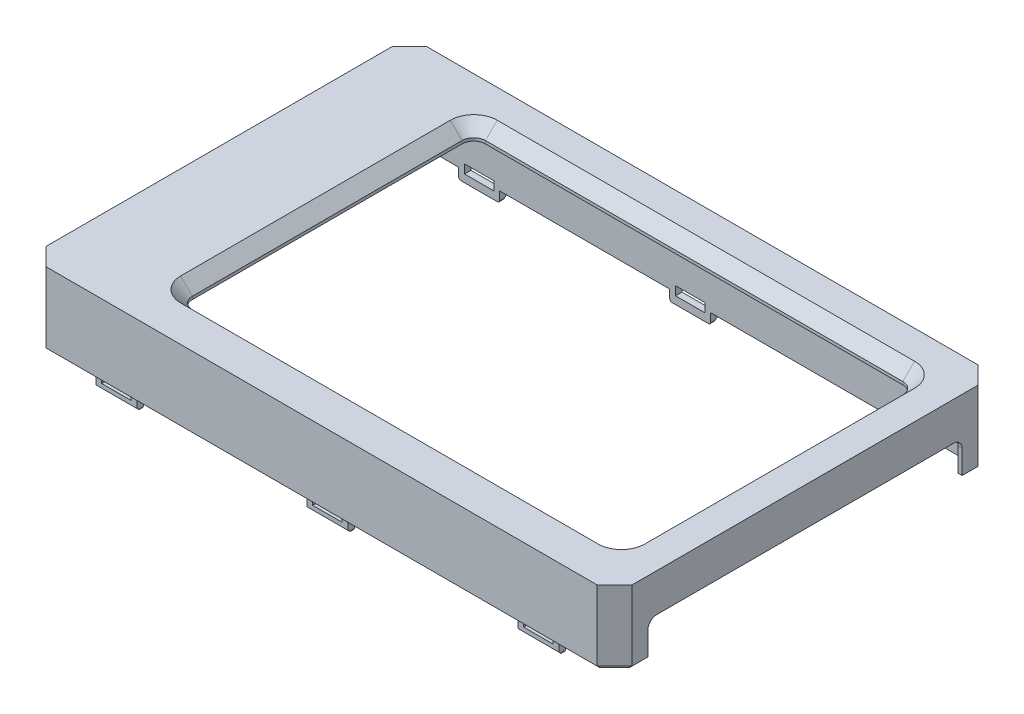
SolidWorks part; units mm, degrees
ref_plane "前视基准面" through (0, 0, 0) normal (0, 0, 1) x (1, 0, 0)
ref_plane "上视基准面" through (0, 0, 0) normal (0, 1, 0) x (1, 0, 0)
ref_plane "右视基准面" through (0, 0, 0) normal (1, 0, 0) x (0, 0, -1)
sketch "草图1" plane through (0, 0, 0) normal (0, 1, 0) x (1, 0, 0)
  line L1 (-50, 32.5) -> (50, 32.5)
  line L2 (-50, 32.5) -> (-50, -32.5)
  line L3 (-50, -32.5) -> (50, -32.5)
  line L4 (50, 32.5) -> (50, -32.5)
  line L5 (-50, 32.5) -> (50, -32.5) construction
  line L6 (-50, -32.5) -> (50, 32.5) construction
  point P0 (0, 0)
  dimension "D1" = 100
  dimension "D2" = 65
extrude "凸台-拉伸1" add sketch "草图1" along normal blind 2
sketch "草图4" plane through (0, 0, 0) normal (0, -1, 0) x (1, 0, 0)
  line L4 (-50, -32.5) -> (50, -32.5)
  line L5 (50, -32.5) -> (50, 32.5)
  line L6 (50, 32.5) -> (-50, 32.5)
  line L7 (-50, 32.5) -> (-50, -32.5)
  line L8 (-47.9, -30.4) -> (47.9, -30.4)
  line L9 (47.9, -30.4) -> (47.9, 30.4)
  line L10 (47.9, 30.4) -> (-47.9, 30.4)
  line L11 (-47.9, 30.4) -> (-47.9, -30.4)
  line L12 (-47.9, -30.4) -> (47.9, -30.4)
  line L13 (47.9, -30.4) -> (47.9, 30.4)
  line L14 (47.9, 30.4) -> (-47.9, 30.4)
  line L15 (-47.9, 30.4) -> (-47.9, -30.4)
  line L16 (-50, -32.5) -> (50, -32.5)
  line L17 (50, -32.5) -> (50, 32.5)
  line L18 (50, 32.5) -> (-50, 32.5)
  line L19 (-50, 32.5) -> (-50, -32.5)
  dimension "D1" = 2.1
  dimension "D2" = 0
extrude "凸台-拉伸2" add sketch "草图4" along normal blind 10
sketch "草图21" plane through (-50, 0, 0) normal (-1, 0, 0) x (0, 0, 1)
  line L0 (-32.5, 2) -> (32.5, 2) construction
  line L1 (-10, -2) -> (10, -2)
  line L2 (-10, -2) -> (-10, -4)
  line L3 (-10, -4) -> (10, -4)
  line L4 (10, -2) -> (10, -4)
  line L5 (-10, -2) -> (10, -4) construction
  line L6 (-10, -4) -> (10, -2) construction
  point P0 (0, -3)
  point P8 (0, 2)
  dimension "D1" = 4
  dimension "D2" = 2
  dimension "D3" = 20
chamfer "倒角4" distance 2 angle 45 4 edges at (47.9, -5, -30.4) (-47.9, -5, -30.4) (-47.9, -5, 30.4) (47.9, -5, 30.4)
chamfer "倒角5" distance 3 angle 45 4 edges at (-50, -4, -32.5) (-50, -4, 32.5) (50, -4, -32.5) (50, -4, 32.5)
sketch "草图24" plane through (47.9, 0, 0) normal (-1, 0, 0) x (0, 0, 1)
  line L0 (-28.4, -10) -> (28.4, -10) construction
  line L1 (-28.3, -10) -> (28.3, -10)
  line L2 (-28.3, -10) -> (-28.3, -4)
  line L3 (-28.3, -4) -> (28.3, -4)
  line L4 (28.3, -10) -> (28.3, -4)
  line L6 (-32.5, 2) -> (-32.5, -10) construction
  line L7 (32.5, -10) -> (32.5, 2) construction
  point P12 (0, 0)
  point P13 (-28.3, -1)
  point P14 (0, 0)
  point P15 (0, 0)
  point P16 (0, 0)
  point P17 (0, 0)
  point P18 (0, 0)
  point P19 (-28.3, -1)
  point P20 (0, 0)
  point P21 (0, 0)
  point P22 (0, 0)
  point P23 (28.3, -1)
  dimension "D1" = 4.2
  dimension "D2" = 4.2
  dimension "D3" = 6
extrude "切除-拉伸8" cut sketch "草图24" against normal blind 1.4
fillet "圆角9" radius 2 2 edges at (48.6, -4, 28.3) (48.6, -4, -28.3)
sketch "草图25" plane through (49.3, 0, 0) normal (-1, 0, 0) x (0, 0, 1)
  line L0 (-32.5, 2) -> (-32.5, -10) construction
  line L1 (32.5, -10) -> (32.5, 2) construction
  line L2 (29.5, -10) -> (-29.5, -10) construction
  line L4 (-28.3, -10) -> (28.3, -10) construction
  line L12 (26.8, -10) -> (26.8, -6)
  line L13 (25.3, -4.5) -> (-25.3, -4.5)
  line L14 (-26.8, -6) -> (-26.8, -10)
  line L15 (-26.8, -10) -> (26.8, -10)
  arc A6 (26.8, -6) -> (25.3, -4.5) centre (25.3, -6) ccw
  arc A7 (-25.3, -4.5) -> (-26.8, -6) centre (-25.3, -6) ccw
  point P0 (26.8, -10)
  dimension "D1" = 7.2
  dimension "D2" = 7.2
  dimension "D3" = 5.5
  dimension "D4" = 4
extrude "切除-拉伸9" cut sketch "草图25" against normal blind 11.4
sketch "草图26" plane through (0, -10, 0) normal (0, -1, 0) x (1, 0, 0)
  line L0 (45.9, 30.4) -> (47.9, 28.4)
  line L1 (-45.9, -30.4) -> (45.9, -30.4)
  line L2 (-47.9, -28.4) -> (-47.9, 28.4)
  line L3 (-45.9, 30.4) -> (45.9, 30.4)
  line L5 (-47.9, 28.4) -> (-45.9, 30.4)
  line L6 (-47.9, -28.4) -> (-45.9, -30.4)
  line L7 (45.9, -30.4) -> (47.9, -28.4)
  line L8 (-49, -28.8556) -> (-49, 28.8556)
  line L9 (-49, 28.8556) -> (-46.3556, 31.5)
  line L10 (-46.3556, 31.5) -> (46.3556, 31.5)
  line L11 (46.3556, 31.5) -> (49, 28.8556)
  line L13 (46.3556, -31.5) -> (49, -28.8556)
  line L14 (-46.3556, -31.5) -> (46.3556, -31.5)
  line L15 (-49, -28.8556) -> (-46.3556, -31.5)
  line L16 (45.9, 30.4) -> (-45.9, 30.4) construction
  line L17 (49, -28.8556) -> (49, 28.8556) construction
  line L18 (47.9, -28.4) -> (47.9, 28.4) construction
  line L19 (49, 28.8556) -> (49, 28.3)
  line L21 (49, 28.3) -> (47.9, 28.3)
  line L23 (47.9, 28.3) -> (47.9, 28.4)
  line L24 (49, -28.8556) -> (49, -28.3)
  line L26 (49, -28.3) -> (47.9, -28.3)
  line L28 (47.9, -28.3) -> (47.9, -28.4)
  line L29 (49.3, -28.3) -> (47.9, -28.3) construction
  line L30 (49.3, 28.3) -> (47.9, 28.3) construction
  point P0 (-47.9, -30.4)
  point P1 (47.9, 30.4)
  point P2 (-47.9, 30.4)
  point P3 (47.9, -30.4)
  dimension "D2" = 56.8
  dimension "D7" = 91.8
  dimension "D1" = 1.1
extrude "凸台-拉伸9" add sketch "草图26" along normal blind 1
sketch "草图30" plane through (0, 0, 0) normal (0, -1, 0) x (1, 0, 0)
  line L0 (50, 25.3) -> (50, -25.3) construction
  line L1 (45.3834, 10.75) -> (47.8, 10.75)
  line L2 (45.3834, 10.75) -> (45.3834, 9.25)
  line L3 (45.3834, 9.25) -> (47.8, 9.25)
  line L4 (47.8, 10.75) -> (47.8, 9.25)
  line L5 (45.3834, -7.25) -> (47.8, -7.25)
  line L6 (45.3834, -7.25) -> (45.3834, -8.75)
  line L7 (45.3834, -8.75) -> (47.8, -8.75)
  line L8 (47.8, -7.25) -> (47.8, -8.75)
  dimension "D1" = 2.2
  dimension "D2" = 2.4166
  dimension "D3" = 1.5
  dimension "D4" = 1.5
extrude "凸台-拉伸10" add sketch "草图30" along normal blind 6.3
chamfer "倒角8" distance 1 angle 45 2 edges at (47.8, -6.3, 10) (47.8, -6.3, -8)
sketch "草图33" plane through (-47.9, 0, 0) normal (1, 0, 0) x (0, 0, -1)
  line L1 (-7.5, -13) -> (-6, -13)
  line L2 (-7.5, -13) -> (-7.5, 0)
  line L3 (-7.5, 0) -> (-6, 0)
  line L4 (-6, -13) -> (-6, 0)
  line L6 (6, -13) -> (7.5, -13)
  line L7 (6, -13) -> (6, 0)
  line L8 (6, 0) -> (7.5, 0)
  line L9 (7.5, -13) -> (7.5, 0)
  line L10 (-32.5, -10) -> (-32.5, 2) construction
  line L11 (32.5, 2) -> (32.5, -10) construction
  line L12 (26.5, 0) -> (28, 0) construction
  line L13 (-28.4, 0) -> (28.4, 0) construction
  dimension "D1" = 25
  dimension "D2" = 25
  dimension "D3" = 13
  dimension "D4" = 1.5
extrude "凸台-拉伸11" add sketch "草图33" along normal blind 2
extrude "切除-拉伸15" cut sketch "草图21" against normal blind 5
fillet "圆角11" radius 1 4 edges at (-48.95, -2, -10) (-48.95, -4, -10) (-48.95, -2, 10) (-48.95, -4, 10)
chamfer "倒角9" distance 1 angle 45 2 edges at (-47.9, -13, 6.75) (-47.9, -13, -6.75)
sketch "草图34" plane through (0, 0, -30.4) normal (0, 0, 1) x (1, 0, 0)
  line L0 (47, -10) -> (-47, -10) construction
  line L1 (32.5, -10) -> (39.5, -10)
  line L2 (32.5, -10) -> (32.5, -12.8)
  line L3 (32.5, -12.8) -> (39.5, -12.8)
  line L4 (39.5, -10) -> (39.5, -12.8)
  line L6 (-3.5, -10) -> (3.5, -10)
  line L7 (-3.5, -10) -> (-3.5, -12.8)
  line L8 (-3.5, -12.8) -> (3.5, -12.8)
  line L9 (3.5, -10) -> (3.5, -12.8)
  line L10 (-39.5, -10) -> (-32.5, -10)
  line L11 (-39.5, -10) -> (-39.5, -12.8)
  line L12 (-39.5, -12.8) -> (-32.5, -12.8)
  line L13 (-32.5, -10) -> (-32.5, -12.8)
  dimension "D1" = 10.5
  dimension "D2" = 7
  dimension "D3" = 29
  dimension "D4" = 2.8
  dimension "D5" = 29
extrude "凸台-拉伸12" add sketch "草图34" against normal blind 1.1
sketch "草图35" plane through (0, 0, 30.4) normal (0, 0, -1) x (-1, 0, 0)
  line L4 (39.5, -10) -> (32.5, -10)
  line L5 (32.5, -10) -> (32.5, -12.8)
  line L6 (32.5, -12.8) -> (39.5, -12.8)
  line L7 (39.5, -12.8) -> (39.5, -10)
  line L8 (39.5, -10) -> (32.5, -10)
  line L9 (32.5, -10) -> (32.5, -12.8)
  line L10 (32.5, -12.8) -> (39.5, -12.8)
  line L11 (39.5, -12.8) -> (39.5, -10)
  line L12 (3.5, -10) -> (-3.5, -10)
  line L13 (-3.5, -10) -> (-3.5, -12.8)
  line L14 (-3.5, -12.8) -> (3.5, -12.8)
  line L15 (3.5, -12.8) -> (3.5, -10)
  line L16 (3.5, -10) -> (-3.5, -10)
  line L17 (-3.5, -10) -> (-3.5, -12.8)
  line L18 (-3.5, -12.8) -> (3.5, -12.8)
  line L19 (3.5, -12.8) -> (3.5, -10)
  line L20 (-32.5, -10) -> (-39.5, -10)
  line L21 (-39.5, -10) -> (-39.5, -12.8)
  line L22 (-39.5, -12.8) -> (-32.5, -12.8)
  line L23 (-32.5, -12.8) -> (-32.5, -10)
  line L24 (-32.5, -10) -> (-39.5, -10)
  line L25 (-39.5, -10) -> (-39.5, -12.8)
  line L26 (-39.5, -12.8) -> (-32.5, -12.8)
  line L27 (-32.5, -12.8) -> (-32.5, -10)
  dimension "D1" = 0
  dimension "D2" = 0
  dimension "D3" = 0
extrude "凸台-拉伸13" add sketch "草图35" against normal blind 1.1
sketch "草图36" plane through (0, 0, 31.5) normal (0, 0, 1) x (1, 0, 0)
  line L0 (46.3556, -10) -> (-46.3556, -10) construction
  line L1 (-33.5, -10) -> (-38.5, -10)
  line L2 (-33.5, -10) -> (-33.5, -11.5)
  line L3 (-33.5, -11.5) -> (-38.5, -11.5)
  line L4 (-38.5, -10) -> (-38.5, -11.5)
  line L5 (-50, -10) -> (-50, 2) construction
  line L6 (2.5, -10) -> (-2.5, -10)
  line L7 (2.5, -10) -> (2.5, -11.5)
  line L8 (2.5, -11.5) -> (-2.5, -11.5)
  line L9 (-2.5, -10) -> (-2.5, -11.5)
  line L10 (38.5, -10) -> (33.5, -10)
  line L11 (38.5, -10) -> (38.5, -11.5)
  line L12 (38.5, -11.5) -> (33.5, -11.5)
  line L13 (33.5, -10) -> (33.5, -11.5)
  point P16 (38.5, -8.5)
  dimension "D1" = 11.5
  dimension "D2" = 5
  dimension "D3" = 1.5
  dimension "D4" = 31
  dimension "D5" = 31
extrude "切除-拉伸16" cut sketch "草图36" against normal up to next
sketch "草图37" plane through (0, 0, -31.5) normal (0, 0, -1) x (-1, 0, 0)
  line L4 (-33.5, -10) -> (-38.5, -10)
  line L5 (-33.5, -11.5) -> (-33.5, -10)
  line L6 (-38.5, -11.5) -> (-33.5, -11.5)
  line L7 (-38.5, -10) -> (-38.5, -11.5)
  line L8 (-33.5, -10) -> (-38.5, -10)
  line L9 (-33.5, -11.5) -> (-33.5, -10)
  line L10 (-38.5, -11.5) -> (-33.5, -11.5)
  line L11 (-38.5, -10) -> (-38.5, -11.5)
  line L12 (2.5, -10) -> (-2.5, -10)
  line L13 (2.5, -11.5) -> (2.5, -10)
  line L14 (-2.5, -11.5) -> (2.5, -11.5)
  line L15 (-2.5, -10) -> (-2.5, -11.5)
  line L16 (2.5, -10) -> (-2.5, -10)
  line L17 (2.5, -11.5) -> (2.5, -10)
  line L18 (-2.5, -11.5) -> (2.5, -11.5)
  line L19 (-2.5, -10) -> (-2.5, -11.5)
  line L20 (38.5, -10) -> (33.5, -10)
  line L21 (38.5, -11.5) -> (38.5, -10)
  line L22 (33.5, -11.5) -> (38.5, -11.5)
  line L23 (33.5, -10) -> (33.5, -11.5)
  line L24 (38.5, -10) -> (33.5, -10)
  line L25 (38.5, -11.5) -> (38.5, -10)
  line L26 (33.5, -11.5) -> (38.5, -11.5)
  line L27 (33.5, -10) -> (33.5, -11.5)
  dimension "D1" = 0
  dimension "D2" = 0
  dimension "D3" = 0
extrude "切除-拉伸17" cut sketch "草图37" against normal up to next
chamfer "倒角11" distance 0.6 angle 45 6 edges at (36, -12.8, -31.5) (-36, -12.8, 31.5) (-36, -12.8, -31.5) (0, -12.8, -31.5) (36, -12.8, 31.5) (0, -12.8, 31.5)
fillet "圆角12" radius 0.4 12 edges at (39.5, -12.8, 30.65) (32.5, -12.8, 30.65) (-3.5, -12.8, 30.65) (3.5, -12.8, 30.65) (-32.5, -12.8, 30.65) (-39.5, -12.8, 30.65) (-39.5, -12.8, -30.65) (-32.5, -12.8, -30.65) (3.5, -12.8, -30.65) (-3.5, -12.8, -30.65) (32.5, -12.8, -30.65) (39.5, -12.8, -30.65)
sketch "草图39" plane through (0, 2, 0) normal (0, 1, 0) x (1, 0, 0)
  line L1 (-32.1526, 25.63) -> (43.0474, 25.63)
  line L2 (-32.1526, 25.63) -> (-32.1526, -24.37)
  line L3 (-32.1526, -24.37) -> (43.0474, -24.37)
  line L4 (43.0474, 25.63) -> (43.0474, -24.37)
  point P4 (44.0553, 24.9188)
  point P5 (43.2384, 25.0379)
  point P6 (46.9, 20.6)
  point P7 (0, 0)
  point P8 (-28.3, 20.6)
  point P12 (43.0474, 25.63)
  dimension "D1" = 75.2
  dimension "D2" = 50
extrude "切除-拉伸18" cut sketch "草图39" against normal up to next
sketch "草图40" plane through (0, 0, 0) normal (0, -1, 0) x (1, 0, 0)
  line L0 (-35.1526, -28.63) -> (46.0474, -28.63)
  line L1 (46.0474, -28.63) -> (46.0474, 27.37)
  line L2 (46.0474, 27.37) -> (-35.1526, 27.37)
  line L3 (-35.1526, 27.37) -> (-35.1526, -28.63)
  line L4 (-32.1526, -25.63) -> (43.0474, -25.63)
  line L5 (43.0474, -25.63) -> (43.0474, 24.37)
  line L6 (43.0474, 24.37) -> (-32.1526, 24.37)
  line L7 (-32.1526, 24.37) -> (-32.1526, -25.63)
  line L8 (-32.1526, -25.63) -> (43.0474, -25.63)
  line L9 (43.0474, -25.63) -> (43.0474, 24.37)
  line L10 (43.0474, 24.37) -> (-32.1526, 24.37)
  line L11 (-32.1526, 24.37) -> (-32.1526, -25.63)
  dimension "D1" = 0
  dimension "D2" = 3
extrude "凸台-拉伸14" add sketch "草图40" along normal blind 0.5
fillet "圆角13" radius 2 4 edges at (-32.1526, 0.75, 24.37) (43.0474, 0.75, 24.37) (43.0474, 0.75, -25.63) (-32.1526, 0.75, -25.63)
chamfer "倒角12" distance 2 angle 45 8 edges at (43.0474, 2, -0.63) (42.4616, 2, -25.0442) (42.4616, 2, 23.7842) (5.4474, 2, -25.63) (5.4474, 2, 24.37) (-31.5668, 2, -25.0442) (-31.5668, 2, 23.7842) (-32.1526, 2, -0.63)
